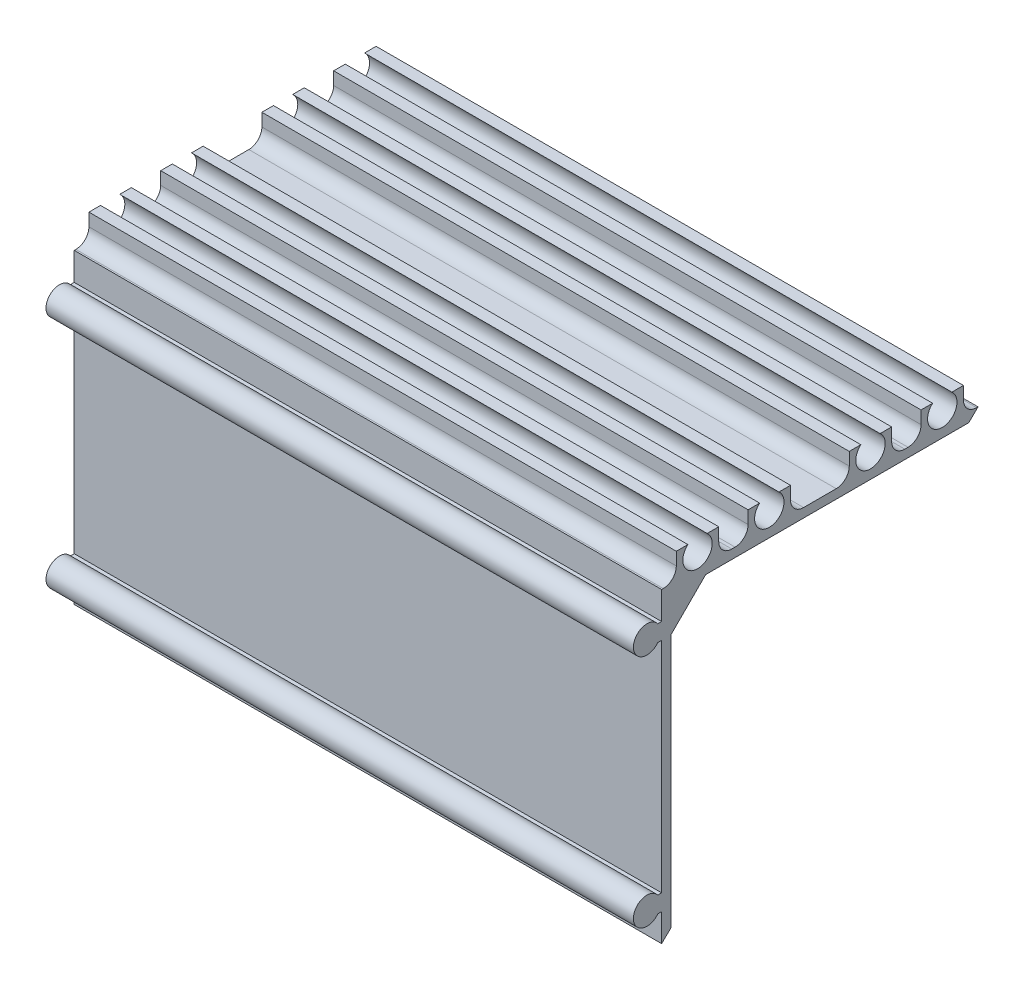
SolidWorks part; units mm, degrees
ref_plane "Спереди" through (0, 0, 0) normal (0, 0, 1) x (1, 0, 0)
ref_plane "Сверху" through (0, 0, 0) normal (0, 1, 0) x (1, 0, 0)
ref_plane "Справа" through (0, 0, 0) normal (1, 0, 0) x (0, 0, -1)
ref_plane "Плоскость4" through (90, 0, 0) normal (1, 0, 0) x (0, 0, -1)
sketch "Эскиз1" plane through (90, 0, 0) normal (1, 0, 0) x (0, 0, -1)
  line L0 (6.75, 160.9062) -> (6.75, 204.25)
  line L1 (6.75, 204.25) -> (-38.0938, 204.25)
  line L2 (-38.0938, 201.75) -> (-37.5, 201.75)
  line L3 (-37.5, 201.75) -> (-37.5, 168.25)
  line L4 (-37.5, 168.25) -> (-38.0938, 168.25)
  line L5 (-38.0938, 165.75) -> (-37.5, 165.75)
  line L6 (-37.5, 165.75) -> (-37.5, 161.5)
  line L7 (-37.5, 161.5) -> (-33.25, 161.5)
  line L8 (-33.25, 161.5) -> (-33.25, 160.9062)
  line L9 (-30.75, 160.9062) -> (-30.75, 161.5)
  line L10 (-30.75, 161.5) -> (-22.25, 161.5)
  line L11 (-22.25, 161.5) -> (-22.25, 160.9062)
  line L12 (-19.75, 160.9062) -> (-19.75, 161.5)
  line L13 (-19.75, 161.5) -> (-6.75, 161.5)
  line L14 (-6.75, 161.5) -> (-6.75, 160.9062)
  line L15 (-4.25, 160.9062) -> (-4.25, 161.5)
  line L16 (-4.25, 161.5) -> (4.25, 161.5)
  line L17 (4.25, 161.5) -> (4.25, 160.9062)
  arc A0 (-38.0938, 204.25) -> (-38.0938, 201.75) centre (-39.75, 203) ccw
  arc A1 (-38.0938, 168.25) -> (-38.0938, 165.75) centre (-39.75, 167) ccw
  arc A2 (-33.25, 160.9062) -> (-30.75, 160.9062) centre (-32, 159.25) ccw
  arc A3 (-22.25, 160.9062) -> (-19.75, 160.9062) centre (-21, 159.25) ccw
  arc A4 (-6.75, 160.9062) -> (-4.25, 160.9062) centre (-5.5, 159.25) ccw
  arc A5 (4.25, 160.9062) -> (6.75, 160.9062) centre (5.5, 159.25) ccw
extrude "Бобышка-Вытянуть1" add sketch "Эскиз1" against normal blind 90
sketch "Эскиз2" plane through (0, 0, -6.75) normal (0, 0, -1) x (-1, 0, 0)
  line L0 (0, 204.25) -> (0, 161.5)
  line L1 (0, 161.5) -> (-90, 161.5)
  line L2 (-90, 161.5) -> (-90, 204.25)
  line L3 (-90, 204.25) -> (0, 204.25)
extrude "Бобышка-Вытянуть2" add sketch "Эскиз2" along normal blind 8.2
sketch "Эскиз3" plane through (0, 204.25, 0) normal (0, 1, 0) x (-1, 0, 0)
  line L0 (-90, -14.95) -> (-90, 37.5)
  line L1 (-90, 37.5) -> (0, 37.5)
  line L2 (0, 37.5) -> (0, -14.95)
  line L3 (0, -14.95) -> (-90, -14.95)
extrude "Бобышка-Вытянуть3" add sketch "Эскиз3" along normal blind 8.2
sketch "Эскиз4" plane through (0, 0, 0) normal (-1, 0, 0) x (0, 0, 1)
  line L0 (-14.95, 161.5) -> (-11, 161.5)
  line L1 (-11, 161.5) -> (-11, 163.75)
  line L2 (-11, 163.75) -> (-14.95, 163.75)
  line L3 (-14.95, 163.75) -> (-14.95, 161.5)
extrude "Вырез-Вытянуть1" cut sketch "Эскиз4" against normal through all
sketch "Эскиз5" plane through (0, 0, 0) normal (-1, 0, 0) x (0, 0, 1)
  line L0 (-14.95, 170.25) -> (-11, 170.25)
  line L1 (-11, 170.25) -> (-11, 199.75)
  line L2 (-11, 199.75) -> (-14.95, 199.75)
  line L3 (-14.95, 199.75) -> (-14.95, 170.25)
extrude "Вырез-Вытянуть2" cut sketch "Эскиз5" against normal through all
sketch "Эскиз6" plane through (0, 0, 0) normal (-1, 0, 0) x (0, 0, 1)
  line L0 (-14.95, 212.45) -> (-14.95, 206.25)
  line L1 (-14.95, 206.25) -> (-11, 206.25)
  line L2 (-11, 206.25) -> (-11, 212.45)
  line L3 (-11, 212.45) -> (-14.95, 212.45)
extrude "Вырез-Вытянуть3" cut sketch "Эскиз6" against normal through all
sketch "Эскиз7" plane through (0, 0, 0) normal (-1, 0, 0) x (0, 0, 1)
  line L0 (-11, 212.45) -> (-11, 208.5)
  line L1 (-11, 208.5) -> (-8.75, 208.5)
  line L2 (-8.75, 208.5) -> (-8.75, 212.45)
  line L3 (-8.75, 212.45) -> (-11, 212.45)
extrude "Вырез-Вытянуть4" cut sketch "Эскиз7" against normal through all
sketch "Эскиз8" plane through (0, 0, 0) normal (-1, 0, 0) x (0, 0, 1)
  line L0 (-2.25, 212.45) -> (-2.25, 208.5)
  line L1 (-2.25, 208.5) -> (2.25, 208.5)
  line L2 (2.25, 208.5) -> (2.25, 212.45)
  line L3 (2.25, 212.45) -> (-2.25, 212.45)
extrude "Вырез-Вытянуть5" cut sketch "Эскиз8" against normal through all
sketch "Эскиз9" plane through (0, 0, 0) normal (-1, 0, 0) x (0, 0, 1)
  line L0 (8.75, 212.45) -> (8.75, 208.5)
  line L1 (8.75, 208.5) -> (17.75, 208.5)
  line L2 (17.75, 208.5) -> (17.75, 212.45)
  line L3 (17.75, 212.45) -> (8.75, 212.45)
extrude "Вырез-Вытянуть6" cut sketch "Эскиз9" against normal through all
sketch "Эскиз10" plane through (0, 0, 0) normal (-1, 0, 0) x (0, 0, 1)
  line L0 (24.25, 212.45) -> (24.25, 208.5)
  line L1 (24.25, 208.5) -> (28.75, 208.5)
  line L2 (28.75, 208.5) -> (28.75, 212.45)
  line L3 (28.75, 212.45) -> (24.25, 212.45)
extrude "Вырез-Вытянуть7" cut sketch "Эскиз10" against normal through all
sketch "Эскиз11" plane through (0, 0, 0) normal (-1, 0, 0) x (0, 0, 1)
  line L0 (37.5, 212.45) -> (35.25, 212.45)
  line L1 (35.25, 212.45) -> (35.25, 208.5)
  line L2 (35.25, 208.5) -> (37.5, 208.5)
  line L3 (37.5, 208.5) -> (37.5, 212.45)
extrude "Вырез-Вытянуть8" cut sketch "Эскиз11" against normal through all
sketch "Эскиз12" plane through (90, 0, 0) normal (1, 0, 0) x (0, 0, -1)
  line L0 (9.6, 207.1) -> (-36.1, 207.1)
  line L1 (-36.1, 207.1) -> (-36.1, 162.9)
  line L2 (-36.1, 162.9) -> (9.6, 162.9)
  line L3 (9.6, 162.9) -> (9.6, 207.1)
extrude "Вырез-Вытянуть9" cut sketch "Эскиз12" against normal blind 86
hole_wizard "Диаметр отверстия Ø2.5 (2.5)1" positions "Эскиз14" profile "Эскиз13" hole size "Ø2.5" standard "Ansi Metric"
sketch "Эскиз14" plane through (90, 0, 0) normal (1, 0, 0) x (0, 0, -1)
  point P0 (5.5, 159.25)
  point P1 (-21, 159.25)
  point P2 (-5.5, 159.25)
  point P3 (-32, 159.25)
  point P4 (-39.75, 167)
  point P5 (-39.75, 203)
sketch "Эскиз13" plane through (90, 159.25, -5.5) normal (0, 1, 0) x (0, 0, -1)
  line L0 (0, 0) -> (0, 90)
  line L1 (0, 90) -> (1.25, 90)
  line L2 (1.25, 90) -> (1.25, 0)
  line L5 (1.25, 0) -> (0, 0)
  line L11 (0, -6.35) -> (0, 107.95) construction
  dimension "Диаметр сквозного отверстия" = 2.5
  dimension "Глубина сквозного отверстия" = 90
hole_wizard "Диаметр отверстия Ø4.5 (4.5)1" positions "Эскиз16" profile "Эскиз15" hole size "Ø4.5" standard "Ansi Metric"
sketch "Эскиз16" plane through (0, 0, 0) normal (-1, 0, 0) x (0, 0, 1)
  point P0 (-13.25, 167)
  point P1 (-13.25, 203)
  point P2 (-5.5, 210.75)
  point P3 (5.5, 210.75)
  point P4 (21, 210.75)
  point P5 (32, 210.75)
sketch "Эскиз15" plane through (0, 167, -13.25) normal (0, 1, 0) x (0, 0, 1)
  line L0 (0, 0) -> (0, 90)
  line L1 (0, 90) -> (2.25, 90)
  line L2 (2.25, 90) -> (2.25, 0)
  line L5 (2.25, 0) -> (0, 0)
  line L11 (0, -6.35) -> (0, 107.95) construction
  dimension "Диаметр сквозного отверстия" = 4.5
  dimension "Глубина сквозного отверстия" = 90
hole_wizard "Диаметр отверстия Ø8.3 (8.3)1" positions "Эскиз18" profile "Эскиз17" hole size "Ø8.3" standard "Ansi Metric"
sketch "Эскиз18" plane through (0, 0, 0) normal (-1, 0, 0) x (0, 0, 1)
  point P0 (13.25, 185)
sketch "Эскиз17" plane through (0, 185, 13.25) normal (0, 1, 0) x (0, 0, 1)
  line L0 (0, 0) -> (0, 3.2)
  line L1 (0, 3.2) -> (4.15, 3.2)
  line L2 (4.15, 3.2) -> (4.15, 0)
  line L5 (4.15, 0) -> (0, 0)
  line L10 (0, 3.2) -> (-4.15, 3.2) construction
  line L11 (0, -6.35) -> (0, 107.95) construction
  dimension "Диаметр отверстия" = 8.3
  dimension "Глубина отверстия" = 3.2
  dimension "Угол заточки сверла" = 180
sketch "Эскиз19" plane through (90, 0, 0) normal (1, 0, 0) x (0, 0, -1)
  circle A0 centre (-39.75, 203) radius 1.6725
  circle A1 centre (-39.75, 167) radius 1.4592
  circle A2 centre (-32, 159.25) radius 1.4599
  circle A3 centre (-21, 159.25) radius 1.5928
  circle A4 centre (-5.5, 159.25) radius 1.5322
  circle A5 centre (5.5, 159.25) radius 1.5961
extrude "Бобышка-Вытянуть4" add sketch "Эскиз19" against normal blind 90
sketch "Эскиз20" plane through (0, 0, 0) normal (-1, 0, 0) x (0, 0, 1)
  circle A0 centre (13.25, 185) radius 4.15
extrude "Вырез-Вытянуть10" cut sketch "Эскиз20" against normal blind 90
fillet "Скругление1" radius 2 1 edges at (45, 208.5, -8.75) type face fillet first side face at (45, 210.475, -8.75) second side face at (45, 208.5, -9.875)
fillet "Скругление2" radius 2 1 edges at (45, 163.75, -11) type face fillet first side face at (45, 162.625, -11) second side face at (45, 163.75, -12.975)
fillet "Скругление3" radius 2 1 edges at (45, 170.25, -11) type face fillet first side face at (45, 185, -11) second side face at (45, 170.25, -12.975)
fillet "Скругление4" radius 2 1 edges at (45, 199.75, -11) type face fillet first side face at (45, 186, -11) second side face at (45, 199.75, -12.975)
fillet "Скругление5" radius 2 1 edges at (45, 206.25, -11) type face fillet first side face at (45, 207.375, -11) second side face at (45, 206.25, -12.975)
fillet "Скругление6" radius 2 1 edges at (45, 208.5, -2.25) type face fillet first side face at (45, 210.475, -2.25) second side face at (45, 208.5, 0)
fillet "Скругление7" radius 2 1 edges at (45, 208.5, 2.25) type face fillet first side face at (45, 210.475, 2.25) second side face at (45, 208.5, 1)
fillet "Скругление8" radius 2 1 edges at (45, 208.5, 8.75) type face fillet first side face at (45, 208.5, 13.25) second side face at (45, 210.475, 8.75)
fillet "Скругление9" radius 2 1 edges at (45, 208.5, 17.75) type face fillet first side face at (45, 208.5, 14.25) second side face at (45, 210.475, 17.75)
fillet "Скругление10" radius 2 1 edges at (45, 208.5, 24.25) type face fillet first side face at (45, 208.5, 26.5) second side face at (45, 210.475, 24.25)
fillet "Скругление11" radius 2 1 edges at (45, 208.5, 28.75) type face fillet first side face at (45, 208.5, 27.5) second side face at (45, 210.475, 28.75)
fillet "Скругление12" radius 2 1 edges at (45, 208.5, 35.25) type face fillet first side face at (45, 208.5, 36.375) second side face at (45, 210.475, 35.25)
fillet "Скругление13" radius 1.2 4 edges at (4, 185, -9.6) (4, 162.9, 13.25) (4, 185, 36.1) (4, 207.1, 13.25) type face fillet first side face at (4, 185, 9.1) second side face at (47, 162.9, 13.25) second side face at (47, 185, -9.6) second side face at (47, 185, 36.1) second side face at (47, 207.1, 13.25)
sketch "Эскиз21" plane through (90, 0, 0) normal (1, 0, 0) x (0, 0, -1)
  line L0 (11, 208.5) -> (-37.5, 161.5)
  line L1 (-37.5, 161.5) -> (-46.0976, 153.1683)
  line L2 (-46.0976, 153.1683) -> (30.2962, 153.1683)
  line L3 (30.2962, 153.1683) -> (30.2962, 229.5069)
  line L4 (30.2962, 229.5069) -> (10.7677, 208.2749)
  point P0 (-37.5, 161.5)
  point P1 (11, 208.5)
extrude "Вырез-Вытянуть12" cut sketch "Эскиз21" against normal blind 150 contours L3 L4 L0 L1 L2 region at (90, 178.1917, -4.9814)
sketch "Эскиз22" plane through (4, 0, 0) normal (1, 0, 0) x (0, 0, -1)
  line L1 (8.317, 205.9) -> (-10.2698, 187.888) construction
  line L2 (-29.9, 205.9) -> (-29.9, 168.8649)
  line L4 (8.317, 205.9) -> (-34.9, 205.9) construction
  line L5 (8.317, 205.9) -> (-29.9, 205.9)
  line L6 (-16.2302, 182.112) -> (-34.817, 164.1) construction
  line L7 (8.317, 205.9) -> (-10.2698, 187.888)
  line L8 (-16.2302, 182.112) -> (-29.9, 168.8649)
  line L9 (-34.9, 205.9) -> (-34.9, 164.1) construction
  arc A0 (-10.2698, 187.888) -> (-16.2302, 182.112) centre (-13.25, 185) ccw construction
  arc A1 (-10.2698, 187.888) -> (-16.2302, 182.112) centre (-13.25, 185) ccw
  point P5 (-24.9, 205.9)
  dimension "D1" = 5
extrude "Вырез-Вытянуть13" cut sketch "Эскиз22" against normal blind 39
sketch "Эскиз23" plane through (4, 0, 0) normal (1, 0, 0) x (0, 0, -1)
  line L0 (-29.9, 205.9) -> (-29.9, 168.8649) construction
  line L1 (-29.9, 205.9) -> (-29.9, 185.9)
  line L2 (8.317, 205.9) -> (-29.9, 205.9) construction
  line L3 (-19.75, 205.9) -> (-29.9, 205.9)
  line L4 (-19.75, 205.9) -> (-29.9, 185.9)
  point P2 (-29.9, 185.9)
  point P4 (-19.75, 205.9)
  dimension "D1" = 20
  dimension "D2" = 10.15
extrude "Бобышка-Вытянуть5" add sketch "Эскиз23" against normal blind 4
sketch "Эскиз24" plane through (90, 0, 0) normal (1, 0, 0) x (0, 0, -1)
  line L0 (-36.1, 207.1) -> (-36.1, 162.9) construction
  line L1 (9.5553, 207.1) -> (-36.1, 207.1) construction
  line L2 (-36.1, 207.1) -> (-36.1, 201.75)
  line L3 (-30.75, 207.1) -> (-36.1, 207.1)
  line L4 (-36.1, 201.75) -> (-30.75, 207.1)
  point P3 (-30.75, 207.1)
  point P4 (-36.1, 201.75)
  dimension "D1" = 5.35
  dimension "D2" = 5.35
extrude "Бобышка-Вытянуть6" add sketch "Эскиз24" against normal blind 88
